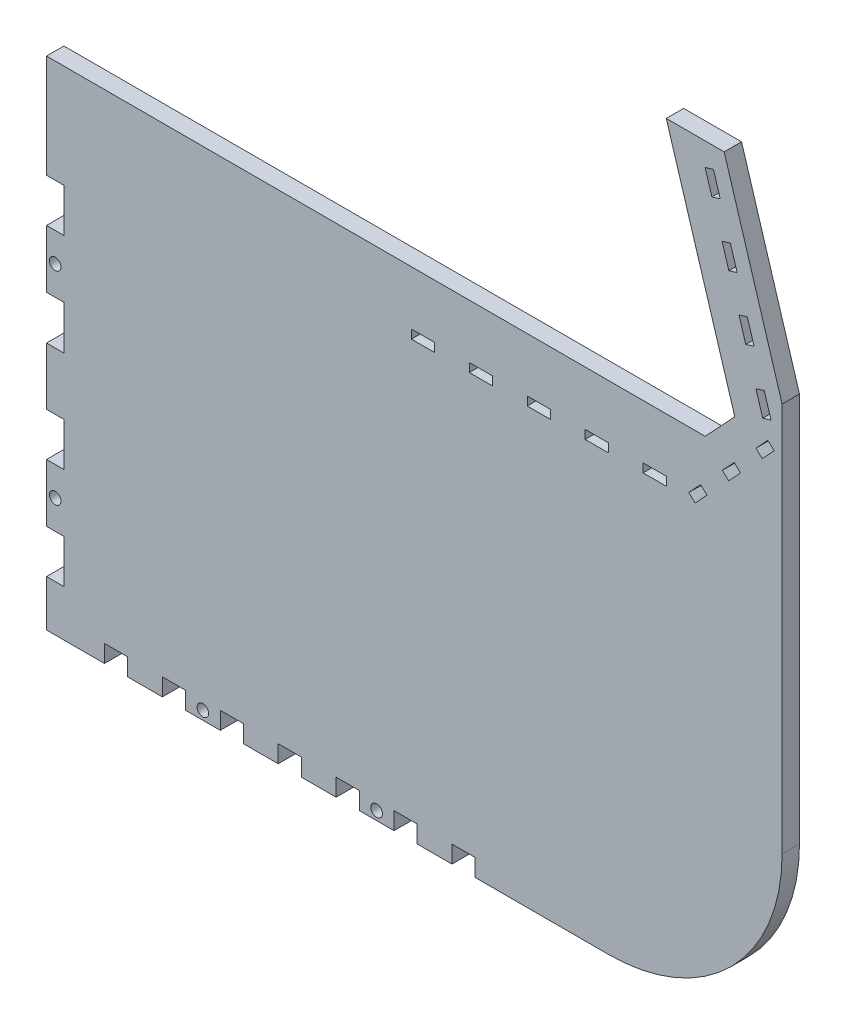
SolidWorks part; units mm, degrees
ref_plane "Plan de face" through (0, 0, 0) normal (0, 0, 1) x (1, 0, 0)
ref_plane "Plan de dessus" through (0, 0, 0) normal (0, 1, 0) x (1, 0, 0)
ref_plane "Plan de droite" through (0, 0, 0) normal (1, 0, 0) x (0, 0, -1)
sketch "Esquisse1" plane through (0, 0, 0) normal (0, 0, 1) x (1, 0, 0)
  line L1 (0, 0) -> (-340, 0)
  line L2 (0, 0) -> (0, 260)
  line L3 (0, 260) -> (-340, 260)
  line L4 (-340, 0) -> (-340, 260)
  line L5 (-340, 0) -> (-340, -49.0561)
  line L6 (0, 0) -> (0, -49.0561)
  point P12 (-170, 0)
  point P13 (-170, 0)
  point P14 (-170, 0)
  dimension "D1" = 340
  dimension "D2" = 260
extrude "Boss.-Extru.1" add sketch "Esquisse1" against normal blind 6
fillet "Congé1" radius 60 2 edges at (0, 0, -3) (-340, 0, -3)
sketch "Esquisse14" plane through (0, 0, -6) normal (0, 0, -1) x (-1, 0, 0)
  line L0 (0, 260) -> (340, 260) construction
  line L1 (145, 260) -> (325, 260)
  line L2 (145, 260) -> (145, 250)
  line L3 (145, 250) -> (325, 250)
  line L4 (325, 260) -> (325, 250)
  line L6 (340, 60) -> (340, 260) construction
  dimension "D1" = 10
  dimension "D2" = 180
  dimension "D3" = 15
extrude "Enlèv. mat.-Extru.7" cut sketch "Esquisse14" against normal blind 10
sketch "Esquisse15" plane through (0, 0, 0) normal (0, 0, 1) x (1, 0, 0)
  line L0 (-325, 250) -> (-145, 250) construction
  line L1 (-310, 250) -> (-190, 250)
  line L2 (-310, 250) -> (-310, 248)
  line L3 (-310, 248) -> (-190, 248)
  line L4 (-190, 250) -> (-190, 248)
  line L5 (-340, 60) -> (-340, 260) construction
  dimension "D1" = 30
  dimension "D2" = 120
  dimension "D3" = 2
extrude "Enlèv. mat.-Extru.8" cut sketch "Esquisse15" against normal blind 10
fillet "Congé2" radius 10 2 edges at (-190, 250, -3) (-310, 250, -3)
fillet "Congé3" radius 8 2 edges at (-145, 260, -3) (-325, 260, -3)
sketch "Esquisse17" plane through (0, 0, 0) normal (0, 0, 1) x (1, 0, 0)
  line L0 (-30, 150) -> (-140, 150)
  line L1 (-25.8174, 254.8022) -> (-23.4785, 247.1518)
  line L2 (-25.8174, 254.8022) -> (-31.5553, 253.048)
  line L3 (0, 260) -> (-137, 260) construction
  line L4 (0, 60) -> (0, 260) construction
  line L5 (-30, 150) -> (-2.7201, 179.2541)
  line L6 (-2.7201, 179.2541) -> (-34.881, 284.4477)
  line L7 (-140, 150) -> (-180, 150)
  line L8 (-180, 150) -> (-205, 193.3013)
  line L9 (-205, 193.3013) -> (-102.154, 315.8684)
  line L10 (-2.7201, 179.2541) -> (-102.154, 315.8684)
  line L11 (-31.6649, 273.9283) -> (-29.3259, 266.2779)
  line L12 (-31.6649, 273.9283) -> (-37.4027, 272.1741)
  line L13 (-29.3259, 266.2779) -> (-35.0637, 264.5237)
  line L14 (-37.4027, 272.1741) -> (-35.0637, 264.5237)
  line L15 (-23.4785, 247.1518) -> (-29.2163, 245.3976)
  line L16 (-31.5553, 253.048) -> (-29.2163, 245.3976)
  line L17 (-19.97, 235.6761) -> (-17.631, 228.0257)
  line L18 (-19.97, 235.6761) -> (-25.7078, 233.9219)
  line L19 (-17.631, 228.0257) -> (-23.3689, 226.2715)
  line L20 (-25.7078, 233.9219) -> (-23.3689, 226.2715)
  line L21 (-14.1226, 216.55) -> (-11.7836, 208.8996)
  line L22 (-14.1226, 216.55) -> (-19.8604, 214.7958)
  line L23 (-11.7836, 208.8996) -> (-17.5214, 207.1454)
  line L24 (-19.8604, 214.7958) -> (-17.5214, 207.1454)
  line L25 (-5.9362, 189.7735) -> (-8.2751, 197.4239)
  line L26 (-5.9362, 189.7735) -> (-11.674, 188.0193)
  line L27 (-8.2751, 197.4239) -> (-14.013, 195.6697)
  line L28 (-11.674, 188.0193) -> (-14.013, 195.6697)
  dimension "D1" = 110
  dimension "D2" = 110
  dimension "D3" = 140
  dimension "D4" = 133
  dimension "D5" = 40
  dimension "D6" = 110
  dimension "D7" = 120
  dimension "D8" = 50
  dimension "D9" = 40
  dimension "D10" = 120
  dimension "D11" = 110
  dimension "D12" = 160
  dimension "D13" = 6
  dimension "D14" = 8
  dimension "D15" = 11
  dimension "D16" = 12
  dimension "D17" = 12
  dimension "D18" = 12
  dimension "D19" = 12
extrude "Enlèv. mat.-Extru.10" cut sketch "Esquisse17" against normal blind 10 contours L26 L28 L10 L9 L8 L7 L0 L5 | L21 L23 L24 L22 | L11 L13 L14 L12 | L1 L15 L16 L2 | L17 L19 L20 L18
sketch "Esquisse18" plane through (0, 0, 0) normal (0, 0, 1) x (1, 0, 0)
  line L0 (-60, 0) -> (-280, 0) construction
  line L1 (-106, 0) -> (-114, 0)
  line L2 (-106, 0) -> (-106, 6)
  line L3 (-106, 6) -> (-114, 6)
  line L4 (-114, 0) -> (-114, 6)
  line L6 (-126, 0) -> (-134, 0)
  line L7 (-126, 0) -> (-126, 6)
  line L8 (-126, 6) -> (-134, 6)
  line L9 (-134, 0) -> (-134, 6)
  line L10 (-146, 0) -> (-154, 0)
  line L11 (-146, 0) -> (-146, 6)
  line L12 (-146, 6) -> (-154, 6)
  line L13 (-154, 0) -> (-154, 6)
  line L14 (-166, 0) -> (-174, 0)
  line L15 (-166, 0) -> (-166, 6)
  line L16 (-166, 6) -> (-174, 6)
  line L17 (-174, 0) -> (-174, 6)
  line L18 (-186, 0) -> (-194, 0)
  line L19 (-186, 0) -> (-186, 6)
  line L20 (-186, 6) -> (-194, 6)
  line L21 (-194, 0) -> (-194, 6)
  line L22 (-206, 0) -> (-214, 0)
  line L23 (-206, 0) -> (-206, 6)
  line L24 (-206, 6) -> (-214, 6)
  line L25 (-214, 0) -> (-214, 6)
  line L26 (-226, 0) -> (-234, 0)
  line L27 (-226, 0) -> (-226, 6)
  line L28 (-226, 6) -> (-234, 6)
  line L29 (-234, 0) -> (-234, 6)
  point P30 (-170, 0)
  point P31 (-170, 0)
  dimension "D1" = 6
  dimension "D2" = 8
  dimension "D3" = 12
  dimension "D4" = 12
  dimension "D5" = 12
  dimension "D6" = 12
  dimension "D7" = 12
  dimension "D8" = 12
extrude "Enlèv. mat.-Extru.11" cut sketch "Esquisse18" against normal blind 10
sketch "Esquisse19" plane through (0, 0, 0) normal (0, 0, 1) x (1, 0, 0)
  line L0 (-61.4905, 260) -> (-2.7201, 179.2541)
  line L1 (-2.7201, 179.2541) -> (0, 179.2541)
  line L2 (0, 260) -> (-61.4905, 260) construction
  line L3 (-27.4065, 260) -> (0, 260)
  line L4 (0, 60) -> (0, 260) construction
  line L5 (0, 260) -> (0, 193.1641)
  line L6 (0, 179.2541) -> (0, 260)
extrude "Enlèv. mat.-Extru.13" cut sketch "Esquisse19" against normal blind 6 contours L0 L1 L6
sketch "Esquisse20" plane through (0, 0, 0) normal (0, 0, 1) x (1, 0, 0)
  line L0 (-192.5, 171.6506) -> (-340, 171.6506)
  line L1 (-180, 150) -> (-205, 193.3013) construction
  line L2 (-340, 60) -> (-340, 260) construction
  line L3 (-192.5, 171.6506) -> (-157.4241, 250)
  line L4 (-157.4241, 250) -> (-157.4241, 260.6427)
  line L5 (-157.4241, 260.6427) -> (-340, 260)
  line L6 (-340, 260) -> (-340, 171.6506)
extrude "Enlèv. mat.-Extru.14" cut sketch "Esquisse20" against normal blind 10
sketch "Esquisse21" plane through (0, 0, 0) normal (0, 0, 1) x (1, 0, 0)
  line L0 (-245, 0) -> (-245, 171.6506)
  line L1 (-234, 0) -> (-280, 0) construction
  line L2 (-340, 171.6506) -> (-192.5, 171.6506) construction
  line L3 (-245, 171.6506) -> (-340, 171.6506)
  line L4 (-340, 171.6506) -> (-340, 0)
  line L5 (-340, 0) -> (-245, 0)
  dimension "D1" = 95
extrude "Enlèv. mat.-Extru.15" cut sketch "Esquisse21" against normal blind 10
sketch "Esquisse23" [suppressed] plane through (0, 0, 0) normal (0, 0, 1) x (1, 0, 0)
  line L0 (0, 179.2541) -> (0, 194.5829)
  line L1 (-21.3425, 264.3912) -> (-142.1688, 150)
  line L2 (-30, 150) -> (-180, 150) construction
  line L3 (-142.1688, 150) -> (-30, 150)
  line L4 (-30, 150) -> (0, 179.2541)
  line L5 (7.3236, 298.6945) -> (130.3204, 415.1407) construction
  line L6 (-99.5151, 495.3317) -> (-101.6878, 502.4385) construction
  line L7 (-21.3425, 264.3912) -> (0, 194.5829)
extrude "Boss.-Extru.2" [suppressed] add sketch "Esquisse23" against normal blind 6
sketch "Esquisse24" [suppressed] plane through (0, 0, 0) normal (0, 0, 1) x (1, 0, 0)
  line L0 (-133.7187, 158) -> (-41.0454, 158)
  line L1 (-21.3425, 264.3912) -> (-142.1688, 150) construction
  line L2 (-41.0454, 158) -> (-18.1377, 182.5656)
  line L3 (-18.1377, 182.5656) -> (-38.2581, 248.3765)
  line L4 (-16.0071, 158) -> (-130.8827, 158) construction
  line L6 (-126.9652, 538.5244) -> (-100.292, 451.2803) construction
  line L7 (134.1533, 345.8776) -> (101.9536, 311.3476) construction
  line L8 (-133.7187, 158) -> (-38.2581, 248.3765)
sketch "Esquisse26" [suppressed] plane through (0, 0, 0) normal (0, 0, 1) x (1, 0, 0)
  line L0 (0, 179.2541) -> (0, 194.5829)
  line L1 (0, 194.5829) -> (-20, 260)
  line L2 (-20, 260) -> (-40, 260)
  line L3 (-40, 260) -> (-180, 150)
  line L4 (-142.1688, 150) -> (-180, 150) construction
  line L5 (-180, 150) -> (-30, 150)
  line L6 (-30, 150) -> (0, 179.2541)
  line L7 (-69.7005, 260) -> (-77.1894, 260) construction
  line L8 (0, 194.5829) -> (-21.3425, 264.3912) construction
  dimension "D1" = 20
sketch "Esquisse27" plane through (0, 0, 0) normal (0, 0, 1) x (1, 0, 0)
  line L0 (0, 179.2541) -> (0, 194.5829)
  line L1 (0, 194.5829) -> (-20, 260)
  line L2 (-20, 260) -> (-40, 260)
  line L4 (-180, 150) -> (-30, 150)
  line L5 (-30, 150) -> (0, 179.2541)
  line L6 (-62.1335, 260) -> (-69.6224, 260) construction
  line L7 (-119.3982, 538.5244) -> (-92.7251, 451.2803) construction
  line L8 (-180, 150) -> (-192.5, 171.6506)
  line L9 (-192.5, 171.6506) -> (-40, 260)
  dimension "D1" = 20
extrude "Boss.-Extru.3" add sketch "Esquisse27" against normal blind 6
sketch "Esquisse29" plane through (0, 0, 0) normal (0, 0, 1) x (1, 0, 0)
  line L0 (-40, 260) -> (-16.3428, 182.6209)
  line L1 (-16.3428, 182.6209) -> (-26.5728, 171.6506)
  line L2 (-26.5728, 171.6506) -> (-192.5, 171.6506)
  line L3 (-192.5, 171.6506) -> (-40, 260)
  line L4 (-8.4401, 158) -> (-123.3158, 158) construction
  line L5 (141.7202, 345.8776) -> (109.5205, 311.3476) construction
  line L6 (-119.3982, 538.5244) -> (-92.7251, 451.2803) construction
  dimension "D1" = 15
extrude "Enlèv. mat.-Extru.18" cut sketch "Esquisse29" against normal blind 6
extrude "Enlèv. mat.-Extru.16" [suppressed] cut sketch "Esquisse24" against normal blind 6
sketch "Esquisse25" plane through (0, 0, 0) normal (0, 0, 1) x (1, 0, 0)
  line L0 (-88, 153) -> (-80, 153) construction
  line L1 (-128, 150) -> (-120, 150)
  line L2 (-128, 150) -> (-128, 153)
  line L3 (-128, 153) -> (-120, 153)
  line L4 (-120, 150) -> (-120, 153)
  line L5 (-108, 153) -> (-100, 153)
  line L6 (-108, 153) -> (-108, 150)
  line L7 (-108, 150) -> (-100, 150)
  line L8 (-100, 153) -> (-100, 150)
  line L9 (-88, 153) -> (-80, 153)
  line L10 (-88, 153) -> (-88, 150)
  line L11 (-88, 150) -> (-80, 150)
  line L12 (-80, 153) -> (-80, 150)
  line L13 (-88, 150) -> (-88, 153) construction
  line L14 (-48, 153) -> (-40, 153) construction
  line L15 (-68, 153) -> (-60, 153)
  line L16 (-68, 153) -> (-68, 150)
  line L17 (-68, 150) -> (-60, 150)
  line L18 (-60, 153) -> (-60, 150)
  line L19 (-48, 153) -> (-40, 153)
  line L20 (-48, 153) -> (-48, 150)
  line L21 (-48, 150) -> (-40, 150)
  line L22 (-40, 153) -> (-40, 150)
  line L23 (-32.2251, 152.0127) -> (-28.1331, 156.4008)
  line L24 (-32.2251, 152.0127) -> (-30.0311, 149.9667)
  line L25 (-28.1331, 156.4008) -> (-25.9391, 154.3548)
  line L26 (-30.0311, 149.9667) -> (-25.9391, 154.3548)
  line L27 (-20.6312, 164.4457) -> (-18.4371, 162.3997)
  line L28 (-20.6312, 164.4457) -> (-16.5392, 168.8338)
  line L29 (-18.4371, 162.3997) -> (-14.3451, 166.7878)
  line L30 (-16.5392, 168.8338) -> (-14.3451, 166.7878)
  line L31 (-6.8431, 174.8327) -> (-9.0372, 176.8787)
  line L32 (-6.8431, 174.8327) -> (-2.7511, 179.2208)
  line L33 (-9.0372, 176.8787) -> (-4.9452, 181.2668)
  line L34 (-2.7511, 179.2208) -> (-4.9452, 181.2668)
  line L35 (-9.0384, 194.6551) -> (-6.1695, 195.5322)
  line L36 (-9.0384, 194.6551) -> (-6.6994, 187.0046)
  line L37 (-6.1695, 195.5322) -> (-3.8305, 187.8818)
  line L38 (-6.6994, 187.0046) -> (-3.8305, 187.8818)
  line L39 (-9.678, 207.0079) -> (-12.5469, 206.1307)
  line L40 (-9.678, 207.0079) -> (-12.0169, 214.6583)
  line L41 (-12.5469, 206.1307) -> (-14.8858, 213.7812)
  line L42 (-12.0169, 214.6583) -> (-14.8858, 213.7812)
  line L43 (-18.3943, 225.2568) -> (-15.5254, 226.134)
  line L44 (-18.3943, 225.2568) -> (-20.7333, 232.9073)
  line L45 (-15.5254, 226.134) -> (-17.8644, 233.7844)
  line L46 (-20.7333, 232.9073) -> (-17.8644, 233.7844)
  line L47 (-15.5254, 226.134) -> (-18.3943, 225.2568) construction
  line L48 (-21.3728, 245.26) -> (-23.7118, 252.9105)
  line L49 (-21.3728, 245.26) -> (-24.2417, 244.3829)
  line L50 (-23.7118, 252.9105) -> (-26.5807, 252.0334)
  line L51 (-24.2417, 244.3829) -> (-26.5807, 252.0334)
  line L52 (-12.5469, 206.1307) -> (-14.8858, 213.7812) construction
  line L53 (-6.6994, 187.0046) -> (-9.0384, 194.6551) construction
extrude "Enlèv. mat.-Extru.17" cut sketch "Esquisse25" against normal blind 6
sketch "Esquisse30" plane through (0, 0, 0) normal (0, 0, 1) x (1, 0, 0)
  line L0 (-245, 0) -> (-245, 171.6506) construction
  line L1 (-245, 0) -> (-254, 0)
  line L2 (-245, 0) -> (-245, 171.6506)
  line L3 (-245, 171.6506) -> (-254, 171.6506)
  line L4 (-254, 0) -> (-254, 171.6506)
  dimension "D1" = 9
extrude "Boss.-Extru.4" add sketch "Esquisse30" against normal blind 6
sketch "Esquisse32" plane through (0, 0, 0) normal (0, 0, 1) x (1, 0, 0)
  line L0 (-254, 171.6506) -> (-254, 0) construction
  line L1 (-248, 136) -> (-254, 136)
  line L2 (-248, 136) -> (-248, 121)
  line L3 (-248, 121) -> (-254, 121)
  line L4 (-254, 136) -> (-254, 121)
  line L5 (-254, 51) -> (-248, 51) construction
  line L6 (-248, 101) -> (-254, 101)
  line L7 (-248, 101) -> (-248, 85.8253)
  line L8 (-248, 85.8253) -> (-254, 85.8253)
  line L9 (-254, 101) -> (-254, 85.8253)
  line L10 (-248, 66) -> (-254, 66)
  line L11 (-248, 66) -> (-248, 51)
  line L12 (-248, 51) -> (-254, 51)
  line L13 (-254, 66) -> (-254, 51)
  line L14 (-254, 121) -> (-248, 121) construction
  line L15 (-248, 31) -> (-254, 31)
  line L16 (-248, 31) -> (-248, 16)
  line L17 (-248, 16) -> (-254, 16)
  line L18 (-254, 31) -> (-254, 16)
  line L19 (-254, 16) -> (-248, 16) construction
extrude "Enlèv. mat.-Extru.19" cut sketch "Esquisse32" against normal blind 6
sketch "Esquisse33" plane through (0, 0, 0) normal (0, 0, 1) x (1, 0, 0)
  line L0 (-134, 0) -> (-146, 0) construction
  line L1 (-194, 0) -> (-206, 0) construction
  line L3 (-194, 6) -> (-194, 0) construction
  line L4 (-146, 0) -> (-146, 6) construction
  line L5 (-254, 51) -> (-254, 31) construction
  line L6 (-254, 121) -> (-254, 101) construction
  line L7 (-248, 31) -> (-254, 31) construction
  line L8 (-248, 101) -> (-254, 101) construction
  circle A0 centre (-200, 3) radius 2
  circle A1 centre (-140, 3) radius 2
  circle A2 centre (-251, 41) radius 2
  circle A3 centre (-251, 111) radius 2
  dimension "D1" = 4
  dimension "D2" = 3
  dimension "D3" = 3
  dimension "D4" = 6
  dimension "D5" = 6
  dimension "D6" = 3
  dimension "D7" = 3
  dimension "D8" = 10
  dimension "D9" = 10
extrude "Enlèv. mat.-Extru.20" cut sketch "Esquisse33" against normal through all
